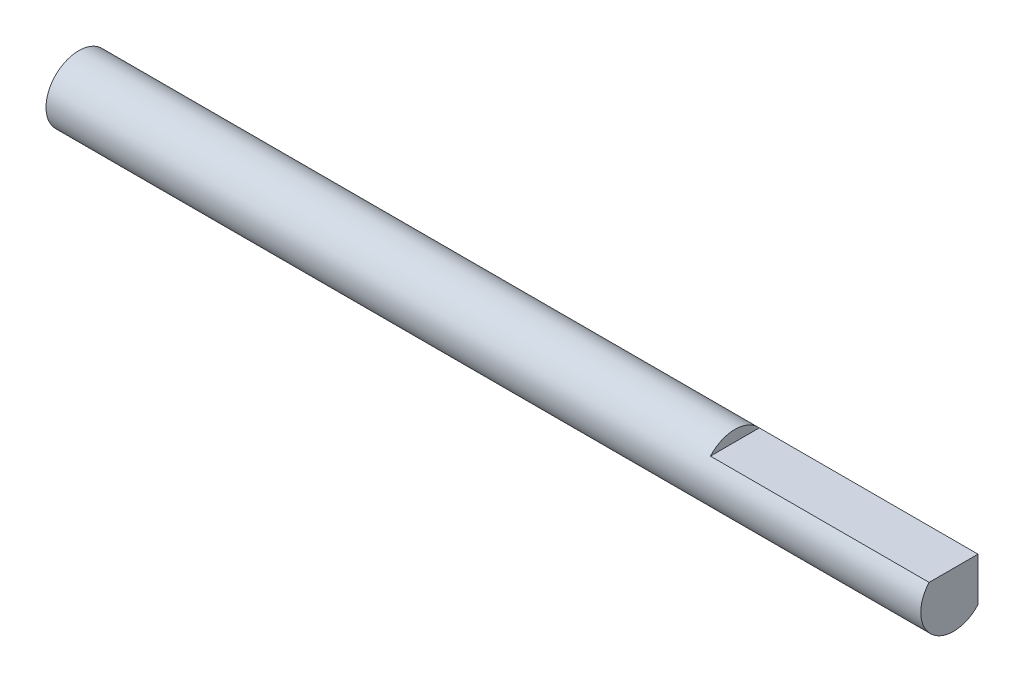
SolidWorks part; units mm, degrees
material "Brass"
ref_plane "Front" through (0, 0, 0) normal (0, 0, 1) x (1, 0, 0)
ref_plane "Top" through (0, 0, 0) normal (0, 1, 0) x (1, 0, 0)
ref_plane "Right" through (0, 0, 0) normal (1, 0, 0) x (0, 0, -1)
sketch "Sketch1" plane through (0, 0, 0) normal (1, 0, 0) x (0, 0, -1)
  circle A0 centre (0, 0) radius 1.5
  dimension "D1" = 3
extrude "Boss-Extrude1" add sketch "Sketch1" along normal mid plane 40
sketch "Sketch2" plane through (20, 0, 0) normal (1, 0, 0) x (0, 0, -1)
  line L0 (1.118, 1) -> (-1.118, 1)
  arc A0 (-1.118, 1) -> (1.118, 1) centre (0, 0) cw
  circle A1 centre (0, 0) radius 1.5 construction
  dimension "D1" = 1
extrude "Cut-Extrude1" cut sketch "Sketch2" against normal blind 10
sketch "Sketch3" plane through (20, 0, 0) normal (1, 0, 0) x (0, 0, -1)
  line L0 (1.118, 1) -> (1.118, -1)
  arc A0 (-1.118, 1) -> (1.118, 1) centre (0, 0) ccw construction
  arc A1 (1.118, 1) -> (1.118, -1) centre (0, 0) cw
extrude "Cut-Extrude2" cut sketch "Sketch3" against normal up to surface (10 mm away) up to face at (10, 1.25, 0)
